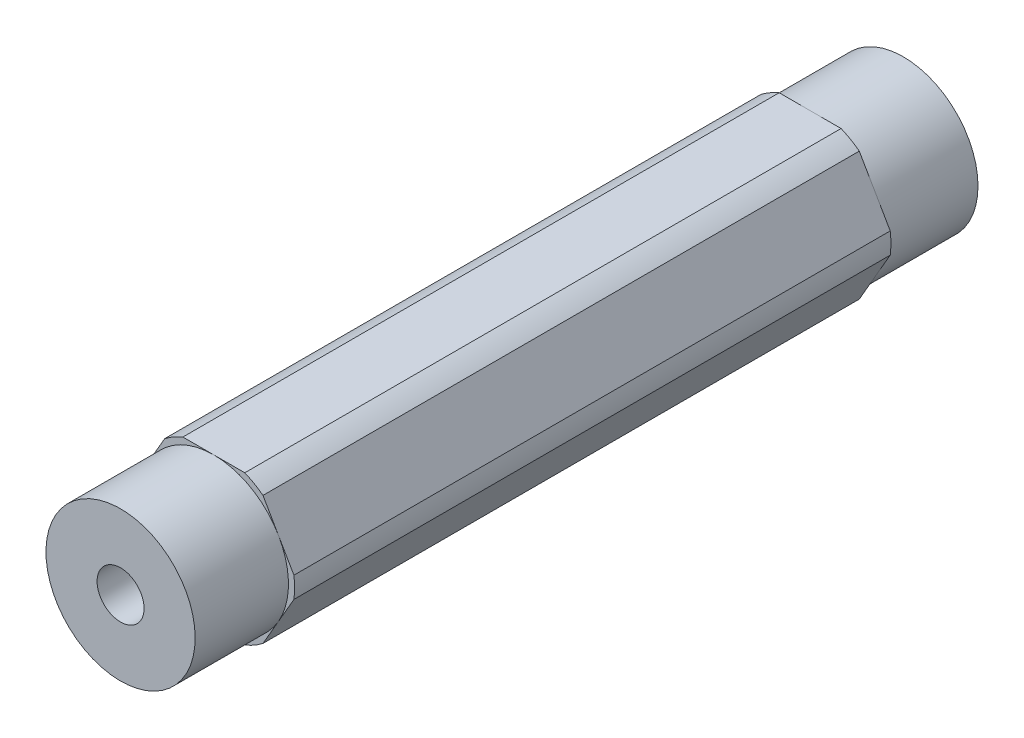
SolidWorks part; units mm, degrees
material "6061-T6 (SS)"
ref_plane "Front Plane" through (0, 0, 0) normal (0, 0, 1) x (1, 0, 0)
ref_plane "Top Plane" through (0, 0, 0) normal (0, 1, 0) x (1, 0, 0)
ref_plane "Right Plane" through (0, 0, 0) normal (1, 0, 0) x (0, 0, -1)
sketch "Sketch1" plane through (0, 0, 0) normal (0, 0, 1) x (1, 0, 0)
  line L1 (3.6662, 6.35) -> (-3.6662, 6.35)
  line L2 (-3.6662, 6.35) -> (-7.3323, 0)
  line L3 (-7.3323, 0) -> (-3.6662, -6.35)
  line L4 (-3.6662, -6.35) -> (3.6662, -6.35)
  line L5 (3.6662, -6.35) -> (7.3323, 0)
  line L6 (7.3323, 0) -> (3.6662, 6.35)
  circle A0 centre (0, 0) radius 6.35 construction
  circle A1 centre (0, 0) radius 2
  circle A2 centre (0, 0) radius 6.875
  point P1 (0, 6.35)
  dimension "D2" = 13.75
  dimension "D3" = 4
  dimension "D1" = 12.7
extrude "Boss-Extrude1" add sketch "Sketch1" along normal mid plane 50.7492 contours L6 A2 L1 L2 L3 L4 L5 A1 region at (3.3439, 5.7918, 0)
sketch "Sketch4" plane through (0, 0, 25.3746) normal (0, 0, 1) x (1, 0, 0)
  circle A0 centre (0, 0) radius 6.35
  circle A1 centre (0, 0) radius 2 construction
  circle A2 centre (0, 0) radius 2
  dimension "D1" = 12.7
extrude "Boss-Extrude2" add sketch "Sketch4" along normal blind 7.9375
mirror "Mirror1" about plane through (0, 0, 0) normal (0, 0, 1) of "Boss-Extrude2"
equation "\"D2@Sketch1\"=13.75mm"
equation "\"D3@Sketch1\"=4mm"
